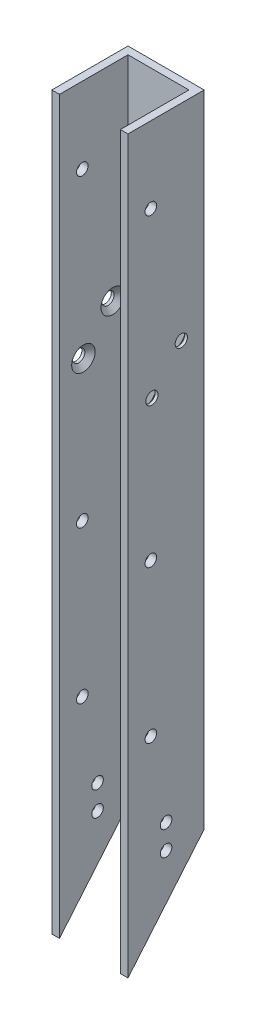
SolidWorks part; units mm, degrees
material "6061-T6 (SS)"
ref_plane "Front Plane" through (0, 0, 0) normal (0, 0, 1) x (1, 0, 0)
ref_plane "Top Plane" through (0, 0, 0) normal (0, 1, 0) x (1, 0, 0)
ref_plane "Right Plane" through (0, 0, 0) normal (1, 0, 0) x (0, 0, -1)
sketch "Sketch1" plane through (0, 0, 0) normal (0, 1, 0) x (1, 0, 0)
  line L0 (-15.875, -15.875) -> (-12.7, -15.875)
  line L2 (15.875, -15.875) -> (15.875, 15.875)
  line L3 (15.875, 15.875) -> (-15.875, 15.875)
  line L4 (-15.875, -15.875) -> (-15.875, 15.875)
  line L5 (15.875, -15.875) -> (-15.875, 15.875) construction
  line L6 (15.875, 15.875) -> (-15.875, -15.875) construction
  line L8 (-12.7, -15.875) -> (-12.7, 12.7)
  line L9 (-12.7, 12.7) -> (12.7, 12.7)
  line L10 (12.7, -15.875) -> (12.7, 12.7)
  line L11 (15.875, -15.875) -> (12.7, -15.875)
  point P0 (0, 0)
  dimension "D1" = 31.75
extrude "Boss-Extrude1" add sketch "Sketch1" along normal blind 304.8 contours L4 L3 L2 L11 L10 L9 L8 L0
sketch "Sketch2" plane through (15.875, 0, 0) normal (1, 0, 0) x (0, 0, -1)
  line L0 (-15.875, 0) -> (15.875, 37.8382)
  line L1 (15.875, 304.8) -> (15.875, 0) construction
  line L2 (-15.875, 0) -> (15.875, 0) construction
  line L3 (15.875, 37.8382) -> (15.875, 0)
  line L4 (15.875, 0) -> (-15.875, 0)
  dimension "D1" = 50
extrude "Cut-Extrude1" cut sketch "Sketch2" against normal through all
sketch "Sketch3" plane through (15.875, 0, 0) normal (1, 0, 0) x (0, 0, -1)
  line L0 (-6.35, 273.05) -> (-6.35, 82.55) construction
  line L1 (15.875, 304.8) -> (15.875, 37.8382) construction
  line L2 (-6.35, 273.05) -> (12.7, 273.05) construction
  line L3 (-15.875, 304.8) -> (15.875, 304.8) construction
  circle A2 centre (-6.35, 273.05) radius 2.413
  circle A3 centre (-6.35, 82.55) radius 2.413
  circle A4 centre (-6.35, 146.05) radius 2.413
  dimension "D5" = 127
  dimension "D3" = 4.826
  dimension "D2" = 31.75
  dimension "D1" = 190.5
  dimension "D4" = 19.05
extrude "Cut-Extrude2" cut sketch "Sketch3" against normal through all both and the other way through all
sketch "Sketch4" plane through (15.875, 0, 0) normal (1, 0, 0) x (0, 0, -1)
  line L2 (-15.875, 0) -> (15.875, 37.8382) construction
  line L3 (0, 58.4345) -> (0, 18.9191) construction
  line L4 (-15.875, 0) -> (15.875, 37.8382) construction
  line L5 (-15.875, 304.8) -> (-15.875, 0) construction
  circle A0 centre (0, 48.2745) radius 2.413
  circle A1 centre (0, 38.1145) radius 2.413
  dimension "D4" = 4.826
  dimension "D5" = 4.826
  dimension "D6" = 10.16
  dimension "D7" = 10.16
extrude "Cut-Extrude3" cut sketch "Sketch4" against normal through all both and the other way through all
sketch "Sketch9" plane through (12.7, 0, 0) normal (-1, 0, 0) x (0, 0, 1)
  line L0 (6.35, 273.05) -> (-32.6592, 240.3174) construction
  line L1 (-12.7, 304.8) -> (-12.7, 34.0544) construction
  line L2 (-27.7007, 244.4781) -> (15.875, 192.5466) construction
  line L3 (15.875, 304.8) -> (15.875, 0) construction
  circle A0 centre (-6.35, 219.0333) radius 2.413
  circle A1 centre (5.8951, 204.4402) radius 2.413
  dimension "D3" = 4.826
  dimension "D4" = 19.05
  dimension "D5" = 6.35
  dimension "D1" = 50
  dimension "D2" = 44.45
hole_wizard "CSK for #10 Flat Head Machine Screw (100)1" positions "Sketch10" profile "Sketch11" countersink size "#10" standard "ANSI Inch" end condition through all
sketch "Sketch10" plane through (12.7, 0, 0) normal (-1, 0, 0) x (0, 0, 1)
  point P0 (-6.35, 219.0333)
  point P3 (5.8951, 204.4402)
sketch "Sketch11" plane through (12.7, 219.0333, -6.35) normal (0, 1, 0) x (0, 0, 1)
  line L0 (0, 0) -> (0, 3.175)
  line L1 (0, 3.175) -> (2.5527, 3.175)
  line L2 (2.5527, 3.175) -> (2.5527, 1.9608)
  line L3 (2.5527, 1.9608) -> (4.8895, 0)
  line L5 (4.8895, 0) -> (0, 0)
  line L6 (-2.5527, 1.9608) -> (-4.8895, 0) construction
  line L11 (0, -6.35) -> (0, 107.95) construction
  dimension "Thru Hole Dia." = 5.1054
  dimension "Thru Hole Depth" = 3.175
  dimension "Near C'Sink Dia." = 9.779
  dimension "Near C'Sink Angle" = 100
mirror "Mirror4" about plane through (0, 0, 0) normal (1, 0, 0) of "CSK for #10 Flat Head Machine Screw (100)1"
